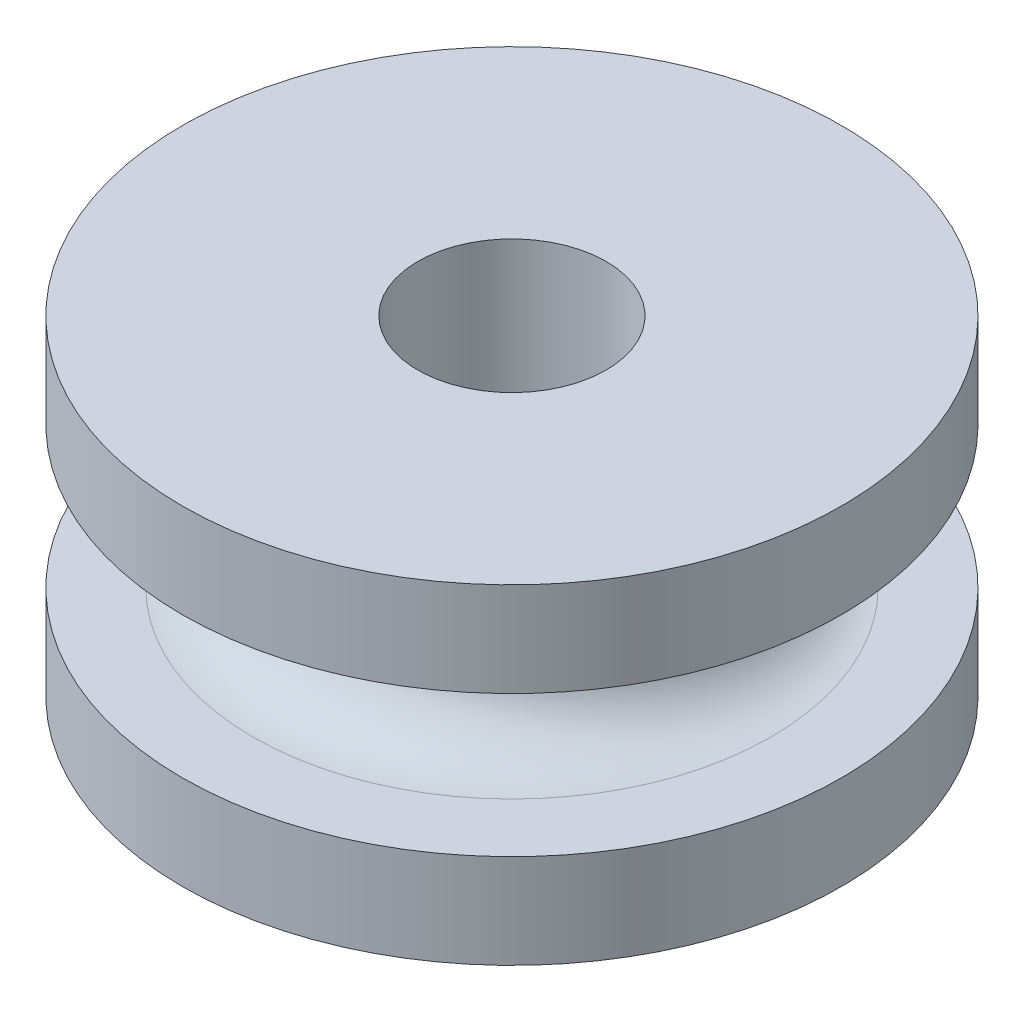
SolidWorks part; units mm, degrees
material "ABS"
ref_plane "正面" through (0, 0, 0) normal (0, 0, 1) x (1, 0, 0)
ref_plane "平面" through (0, 0, 0) normal (0, 1, 0) x (1, 0, 0)
ref_plane "右側面" through (0, 0, 0) normal (1, 0, 0) x (0, 0, -1)
sketch "ｽｹｯﾁ1" plane through (0, 0, 0) normal (0, 0, 1) x (1, 0, 0)
  line L0 (0, 0) -> (0, 6) construction
  line L1 (0, 3.5) -> (-7, 3.5)
  line L2 (-7, 3.5) -> (-7, 1.5)
  line L3 (-7, 1.5) -> (-5.5, 1.5)
  line L4 (-4, 0) -> (0, 0) construction
  line L5 (-7, -3.5) -> (-7, -1.5)
  line L6 (-7, -1.5) -> (-5.5, -1.5)
  line L7 (0, -3.5) -> (-7, -3.5)
  line L8 (0, 3.5) -> (0, -3.5)
  arc A0 (-5.5, 1.5) -> (-5.5, -1.5) centre (-5.5, 0) cw
  dimension "D1" = 3.5
  dimension "D2" = 1.5
  dimension "D3" = 4
  dimension "D4" = 7
revolve "回転1" add sketch "ｽｹｯﾁ1" angle 360 about L8
sketch "ｽｹｯﾁ2" plane through (0, -3.5, 0) normal (0, -1, 0) x (1, 0, 0)
  circle A0 centre (0, 0) radius 2
  dimension "D1" = 4
extrude "ｶｯﾄ - 押し出し1" cut sketch "ｽｹｯﾁ2" against normal through all
